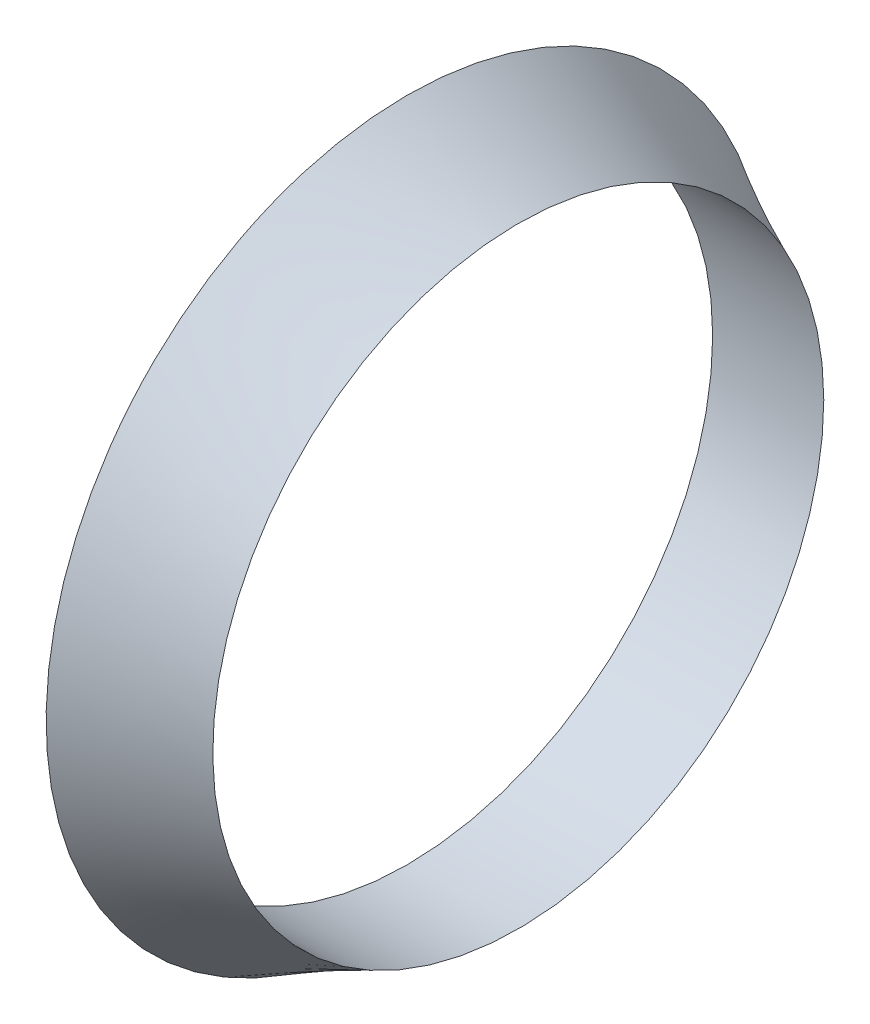
SolidWorks part; units mm, degrees
ref_plane "Front Plane" through (0, 0, 0) normal (0, 0, 1) x (1, 0, 0)
ref_plane "Top Plane" through (0, 0, 0) normal (0, 1, 0) x (1, 0, 0)
ref_plane "Right Plane" through (0, 0, 0) normal (1, 0, 0) x (0, 0, -1)
sketch "Sketch1" plane through (0, 0, 0) normal (1, 0, 0) x (0, 0, -1)
  circle A0 centre (0, 0) radius 65
  dimension "D1" = 130
ref_plane "Plane1" through (20, 0, 0) normal (-1, 0, 0) x (0, 0, 1)
sketch "Sketch2" plane through (20, 0, 0) normal (-1, 0, 0) x (0, 0, 1)
  circle A0 centre (0, 0) radius 55
  dimension "D1" = 110
loft "Loft1" add profiles "Sketch2", "Sketch1" connector at (20, -35.7984, -41.7549) connector at (0, -52.5621, -38.2391)
sketch "Sketch3" plane through (20, 0, 0) normal (1, 0, 0) x (0, 0, -1)
  circle A1 centre (0, 0) radius 55
  circle A2 centre (0, 0) radius 55
  dimension "D1" = 0
extrude "Cut-Extrude1" cut sketch "Sketch3" against normal blind 30
